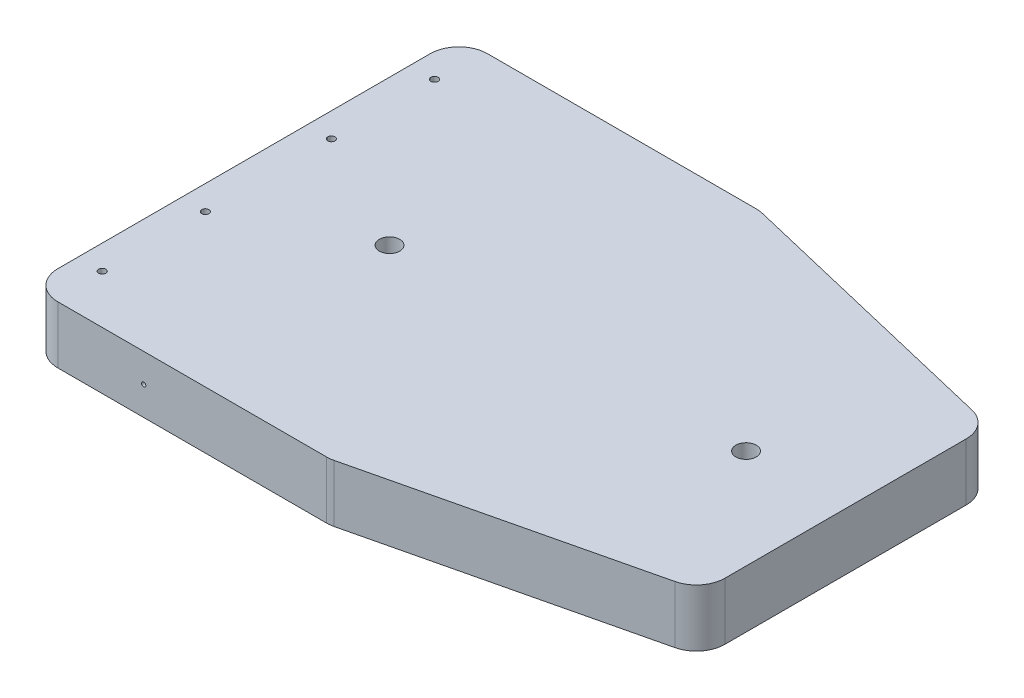
SolidWorks part; units mm, degrees
material "Carvalho"
ref_plane "Plano frontal" through (0, 0, 0) normal (0, 0, 1) x (1, 0, 0)
ref_plane "Plano superior" through (0, 0, 0) normal (0, 1, 0) x (1, 0, 0)
ref_plane "Plano direito" through (0, 0, 0) normal (1, 0, 0) x (0, 0, -1)
sketch "Esboço1" plane through (0, 0, 0) normal (0, 1, 0) x (1, 0, 0)
  line L0 (210, 50) -> (105, 75)
  line L1 (0, -75) -> (105, -75)
  line L2 (0, -75) -> (0, 75)
  line L3 (0, 75) -> (105, 75)
  line L4 (210, -50) -> (210, 50)
  line L5 (195, -38.5714) -> (210, -38.5714) construction
  line L6 (195, -38.5714) -> (195, -53.5714) construction
  line L7 (105, -75) -> (210, -50)
  line L8 (-14.8259, 0) -> (14.392, 0) construction
  line L9 (0, 21.2472) -> (0, -16.7598) construction
  circle A0 centre (50.8, 0) radius 3.5719
  circle A1 centre (175.26, 0) radius 3.57
  circle A2 centre (8.5, -58) radius 1.25
  circle A3 centre (8.5, -22) radius 1.25
  circle A4 centre (8.5, 22) radius 1.25
  circle A5 centre (8.5, 58) radius 1.25
  circle A6 centre (195, -38.5714) radius 0.5
  circle A7 centre (195, 38.5714) radius 0.5
  point P0 (0, 0)
  dimension "D3" = 7.1437
  dimension "D5" = 7.14
  dimension "D9" = 1
  dimension "D12" = 2.5
  dimension "D1" = 25
  dimension "D2" = 150
  dimension "D4" = 50.8
  dimension "D6" = 210
  dimension "D7" = 175.26
  dimension "D8" = 105
  dimension "D10" = 15
  dimension "D11" = 15
extrude "Ressalto-extrusão1" add sketch "Esboço1" along normal blind 15 and the other way blind 5 contours L1 L7 L4 L0 L3 L2 A0 A1 A2 A3 A4 A5 A6 A7 | A6 | A7 region at (98.6526, 0, 0)
fillet "Filete1" radius 10 6 edges at (0, 5, 75) (105, 5, 75) (210, 5, 50) (210, 5, -50) (0, 5, -75) (105, 5, -75)
sketch "Esboço6" plane through (0, 15, 0) normal (0, 1, 0) x (1, 0, 0)
  line L0 (200, 42.1014) -> (200, -42.1014)
  line L2 (65, -65) -> (65, 65)
  line L4 (210, -42.1014) -> (210, 42.1014) construction
  line L5 (202.3162, 51.8295) -> (106.1421, 74.7281) construction
  line L8 (-4.1061, 0) -> (243.1802, 0) construction
  line L9 (65, 65) -> (103.8259, 65)
  line L10 (103.8259, 65) -> (200, 42.1014)
  line L11 (65, -65) -> (103.8259, -65)
  line L12 (103.8259, -65) -> (200, -42.1014)
  line L15 (176.1581, -27.219) -> (200, -21.5423)
  line L17 (103.8259, 75) -> (10, 75) construction
  line L18 (0, 65) -> (0, -65) construction
  line L19 (176.1581, 27.219) -> (200, 21.5423)
  arc A0 (176.1581, -27.219) -> (176.1581, 27.219) centre (175.26, 0) cw
  circle A2 centre (175.26, 0) radius 3.57 construction
  point P24 (176.1581, 27.219)
  dimension "D1" = 10
  dimension "D2" = 10
  dimension "D3" = 10
  dimension "D4" = 65
  dimension "D5" = 20
extrude "Corte-extrusão2" cut sketch "Esboço6" along normal blind 10 from surface contours L2 L8 A0 L19 L0 L10 L9 | L8 L2 L11 L12 L0 L15 A0 region at (118.5775, 15, -32.0455) region at (118.5775, 15, 32.0455) starting at face at (105.3184, -5, 0)
fillet "Filete2" radius 10 9 edges at (65, 0, 65) (65, 0, -65) (103.8259, 0, -65) (200, 0, -21.5423) (176.1581, 0, -27.219) (200, 0, -42.1014) (200, 0, 42.1014) (176.1581, 0, 27.219) (200, 0, 21.5423)
sketch "Esboço7" plane through (0, 0, -75) normal (0, 0, -1) x (-1, 0, 0)
  line L0 (0, 15) -> (0, -5) construction
  line L1 (-40, 15) -> (-40, -5) construction
  line L2 (-10, 15) -> (-103.8259, 15) construction
  line L3 (-10, -5) -> (-103.8259, -5) construction
  circle A0 centre (-40, 5) radius 0.75
  point P10 (0, 0)
  dimension "D2" = 1.5
  dimension "D1" = 40
extrude "Corte-extrusão3" cut sketch "Esboço7" against normal through all
